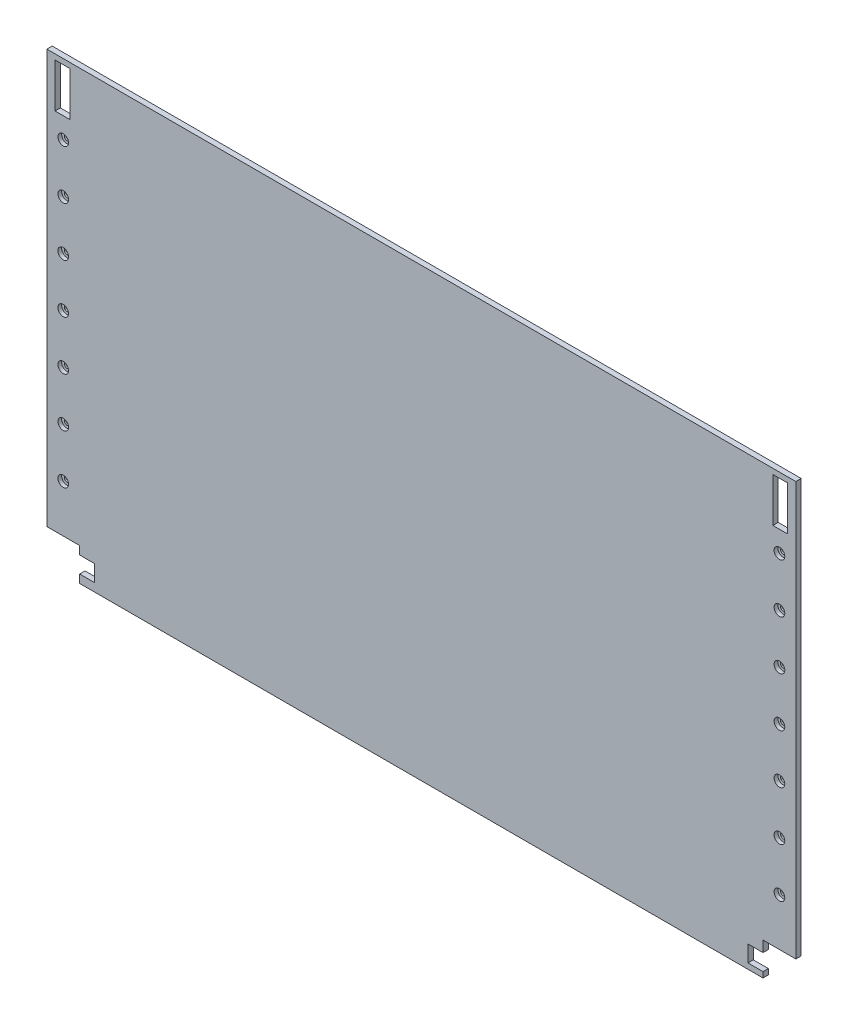
SolidWorks part; units mm, degrees
ref_plane "Plan de face" through (0, 0, 0) normal (0, 0, 1) x (1, 0, 0)
ref_plane "Plan de dessus" through (0, 0, 0) normal (0, 1, 0) x (1, 0, 0)
ref_plane "Plan de droite" through (0, 0, 0) normal (1, 0, 0) x (0, 0, -1)
sketch "Esquisse1" plane through (0, 0, 0) normal (0, 0, 1) x (1, 0, 0)
  line L0 (416, -251.75) -> (-416, -251.75)
  line L1 (-456, -251.75) -> (456, -251.75)
  line L2 (-456, -251.75) -> (-456, 251.75)
  line L3 (-456, 251.75) -> (456, 251.75)
  line L4 (456, -251.75) -> (456, 251.75)
  line L5 (-456, -251.75) -> (456, 251.75) construction
  line L6 (-456, 251.75) -> (456, -251.75) construction
  line L7 (416, -251.75) -> (416, -291.75)
  line L8 (-416, -251.75) -> (-416, -291.75)
  line L9 (416, -291.75) -> (-416, -291.75)
  line L10 (-416, -261.75) -> (-416, -281.75)
  line L11 (-416, -261.75) -> (-397.6701, -261.75)
  line L12 (-416, -281.75) -> (-397.6701, -281.75)
  line L13 (-397.6701, -261.75) -> (-397.6701, -281.75)
  line L14 (397.67, -285) -> (421.0907, -285)
  line L15 (421.0907, -265) -> (421.0907, -285)
  line L16 (397.67, -265) -> (421.0907, -265)
  line L17 (1229.67, -288.5) -> (397.67, -288.5)
  line L18 (397.67, -265) -> (397.67, -285)
  point P0 (0, 0)
  dimension "D1" = 912
  dimension "D2" = 503.5
  dimension "D3" = 40
  dimension "D4" = 40
  dimension "D5" = 40
  dimension "D6" = 10
  dimension "D7" = 20
  dimension "D8" = 18.3299
extrude "Boss.-Extru.1" add sketch "Esquisse1" along normal blind 6.5 contours L11 L13 L12 L8 L9 L7 L0 L18 L16 L15 L14 | L1 L4 L3 L2 L0 region at (0, -271.7134, 0) region at (0, 0, 0)
sketch "Esquisse2" plane through (0, 0, 6.5) normal (0, 0, 1) x (1, 0, 0)
  line L0 (-446, 245.25) -> (-428, 245.25)
  line L1 (-446, 245.25) -> (-446, 191.4632)
  line L2 (-428, 245.25) -> (-428, 191.4632)
  line L3 (-446, 191.4632) -> (-428, 191.4632)
  line L4 (-456, 251.75) -> (456, 251.75) construction
  dimension "D1" = 6.5
extrude "Enlèv. mat.-Extru.1" cut sketch "Esquisse2" against normal blind 6.5
ref_point "Point1"
ref_axis "Axe1" through (0, 251.75, 3.25) along (0, 1, 0)
ref_plane "Plan1" through (0, 0, 0) normal (1, 0, 0) x (0, 1, 0)
mirror "Symétrie1" about plane through (0, 0, 0) normal (1, 0, 0) of "Enlèv. mat.-Extru.1"
hole_wizard "Dégagement M61" positions "Esquisse4" profile "Esquisse3" hole size "M6" standard "JIS" end condition through all
sketch "Esquisse4" plane through (0, 0, 0) normal (0, 0, -1) x (-1, 0, 0)
  point P0 (436.0253, 166.0315)
sketch "Esquisse3" plane through (-436.0253, 166.0315, 0) normal (1, 0, 0) x (0, 1, 0)
  line L0 (0, 0) -> (0, 6.5)
  line L1 (0, 6.5) -> (3.3, 6.5)
  line L2 (3.3, 6.5) -> (3.3, 0)
  line L5 (3.3, 0) -> (0, 0)
  line L11 (0, -6.35) -> (0, 107.95) construction
  dimension "Diamètre du perçage jusqu'au prochain" = 6.6
  dimension "Profondeur du perçage jusqu'au prochain" = 6.5
hole_wizard "Chambrage pour vis à tête ronde bombée M61" positions "Esquisse6" profile "Esquisse5" counterbore size "M6" standard "Ansi Metric" end condition through all
sketch "Esquisse6" plane through (0, 0, 6.5) normal (0, 0, 1) x (1, 0, 0)
  point P0 (-436.0253, 166.0315)
sketch "Esquisse5" plane through (-436.0253, 166.0315, 6.5) normal (1, 0, 0) x (0, -1, 0)
  line L0 (0, 0) -> (0, 6.5)
  line L1 (0, 6.5) -> (3.3, 6.5)
  line L2 (3.3, 4.625) -> (3.3, 6.5)
  line L3 (3.3, 4.625) -> (3.325, 4.6)
  line L4 (3.325, 4.6) -> (6.5, 4.6)
  line L5 (6.5, 4.6) -> (6.5, 0)
  line L7 (0, 0) -> (6.5, 0)
  line L9 (-3.3, 4.625) -> (-3.325, 4.6) construction
  line L11 (0, -6.35) -> (0, 107.95) construction
  dimension "Diamètre du perçage jusqu'au prochain" = 6.6
  dimension "Profondeur du perçage jusqu'au prochain" = 6.5
  dimension "Diamètre du chambrage" = 13
  dimension "Profondeur du chambrage" = 4.6
  dimension "Diamètre du fraisage milieu" = 6.65
  dimension "Angle du fraisage milieu" = 90
pattern_linear "Répétition linéaire1" count 7 spacing 60 along (0, -1, 0) of "Chambrage pour vis à tête ronde bombée M61"
mirror "Symétrie2" about plane through (0, 0, 0) normal (1, 0, 0) of "Répétition linéaire1"
